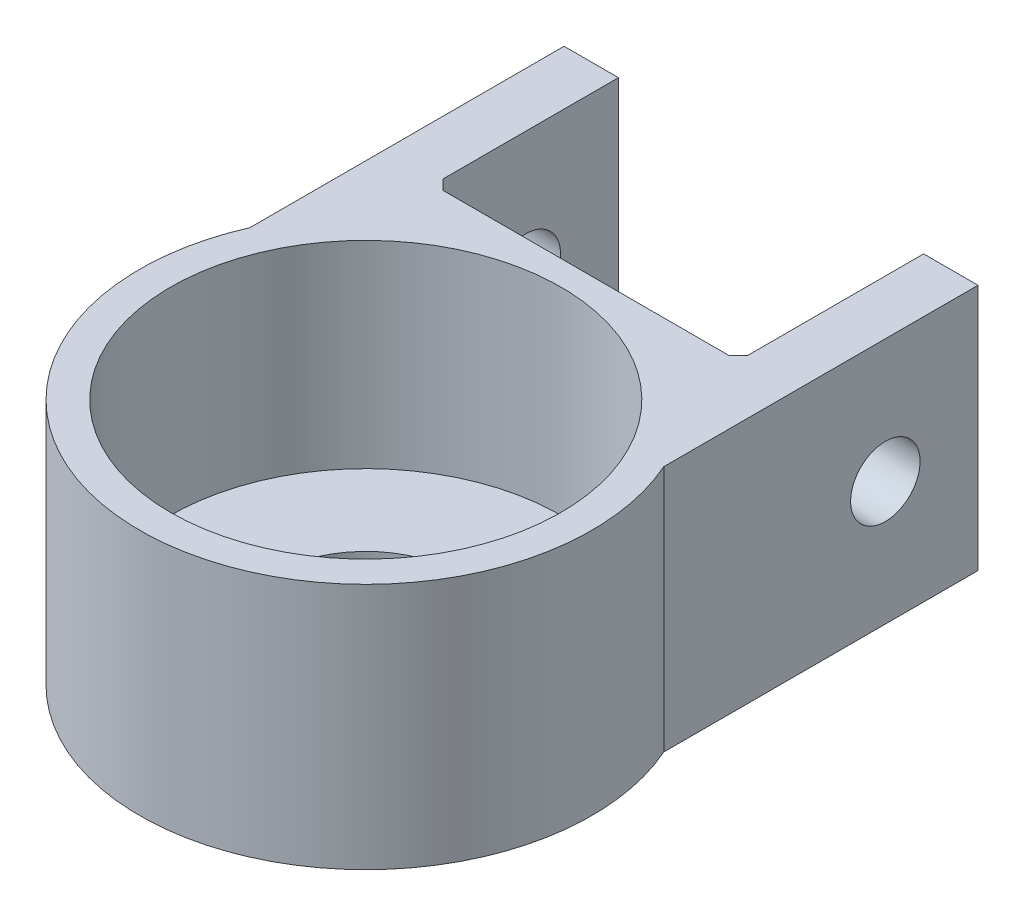
SolidWorks part; units mm, degrees
ref_plane "Front Plane" through (0, 0, 0) normal (0, 0, 1) x (1, 0, 0)
ref_plane "Top Plane" through (0, 0, 0) normal (0, 1, 0) x (1, 0, 0)
ref_plane "Right Plane" through (0, 0, 0) normal (1, 0, 0) x (0, 0, -1)
sketch "Sketch1" plane through (0, 0, 0) normal (0, 1, 0) x (1, 0, 0)
  circle A0 centre (0, 0) radius 23.241
  circle A1 centre (0, 0) radius 9.652
  dimension "D1" = 19.304
  dimension "D2" = 46.482
extrude "Boss-Extrude1" add sketch "Sketch1" along normal blind 5.08
sketch "Sketch2" plane through (0, 5.08, 0) normal (0, 1, 0) x (1, 0, 0)
  line L0 (-21.2725, 9.3608) -> (-21.2725, 41.656)
  line L1 (-21.2725, 41.656) -> (-15.6845, 41.656)
  line L2 (-15.6845, 41.656) -> (-15.6845, 22.606)
  line L3 (-15.6845, 22.606) -> (15.6845, 22.606)
  line L4 (15.6845, 22.606) -> (15.6845, 41.656)
  line L5 (15.6845, 41.656) -> (21.2725, 41.656)
  line L6 (21.2725, 41.656) -> (21.2725, 9.3608)
  line L7 (0, 22.606) -> (0, 0) construction
  arc A0 (-21.2725, 9.3608) -> (21.2725, 9.3608) centre (0, 0) ccw
  circle A1 centre (0, 0) radius 20.066
  circle A2 centre (0, 0) radius 23.241 construction
  point P8 (0, 20.066)
  dimension "D1" = 3.175
  dimension "D2" = 31.369
  dimension "D3" = 5.588
  dimension "D4" = 2.54
  dimension "D5" = 19.05
extrude "Boss-Extrude2" add sketch "Sketch2" along normal offset from surface 25.4 and the other way up to surface (5.08 mm away) up to face at (0, 0, 23.241) other way up to face at (0, 0, 23.241)
sketch "Sketch3" plane through (-21.2725, 0, 0) normal (-1, 0, 0) x (0, 0, 1)
  line L0 (-9.3608, 0) -> (-41.656, 0) construction
  line L1 (-41.656, 25.4) -> (-22.606, 25.4) construction
  line L2 (-41.656, 25.4) -> (-41.656, 0) construction
  line L3 (-41.656, 0) -> (-22.606, 0) construction
  line L4 (-22.606, 25.4) -> (-22.606, 0) construction
  line L5 (-41.656, 25.4) -> (-22.606, 0) construction
  line L6 (-41.656, 0) -> (-22.606, 25.4) construction
  point P4 (-32.131, 12.7)
  dimension "D1" = 19.05
hole_wizard "1/4 Clearance Hole1" positions "Sketch3" profile "Sketch4" hole size "1/4" standard "ANSI Inch" end condition through all
sketch "Sketch4" plane through (-21.2725, 12.7, -32.131) normal (0, 1, 0) x (0, 0, 1)
  line L0 (0, 0) -> (0, 44.5135)
  line L1 (0, 44.5135) -> (3.5712, 44.5135)
  line L2 (3.5712, 44.5135) -> (3.5712, 0)
  line L5 (3.5712, 0) -> (0, 0)
  line L11 (0, -6.35) -> (0, 107.95) construction
  dimension "Thru Hole Dia." = 7.1425
  dimension "Thru Hole Depth" = 44.5135
sketch "Sketch5" plane through (0, 25.4, 0) normal (0, 1, 0) x (1, 0, 0)
  line L1 (-15.6845, 22.606) -> (15.6845, 22.606)
  line L2 (-15.6845, 22.606) -> (-15.6845, 41.656)
  line L3 (-15.6845, 41.656) -> (15.6845, 41.656)
  line L4 (15.6845, 22.606) -> (15.6845, 41.656)
  line L5 (-15.6845, 22.606) -> (15.6845, 41.656) construction
  line L6 (-15.6845, 41.656) -> (15.6845, 22.606) construction
  point P4 (0, 32.131)
extrude "Cut-Extrude1" cut sketch "Sketch5" against normal through all
chamfer "Chamfer1" distance 1 angle 45 2 edges at (15.6845, 12.7, -22.606) (-15.6845, 12.7, -22.606)
equation "\"Body Size\"= 1.56in"
equation "\"clearance\"= 0.01in"
equation "\"Wall thickness\"= 0.125in"
equation "\"D2@Sketch1\"=\"Body Size\"+\"clearance\"*2 +\"Wall thickness\"*2"
